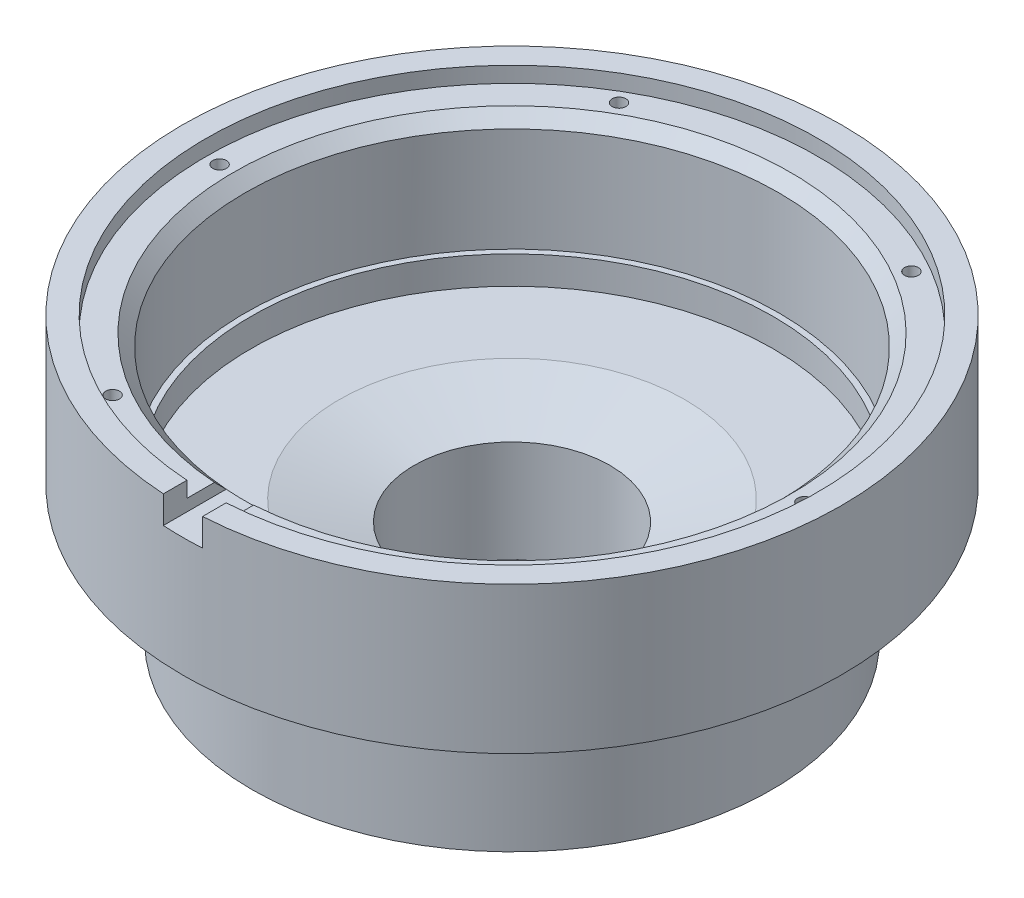
SolidWorks part; units mm, degrees
material "1060 Alloy"
ref_plane "Front Plane" through (0, 0, 0) normal (0, 0, 1) x (1, 0, 0)
ref_plane "Top Plane" through (0, 0, 0) normal (0, 1, 0) x (1, 0, 0)
ref_plane "Right Plane" through (0, 0, 0) normal (1, 0, 0) x (0, 0, -1)
sketch "Sketch7" plane through (0, 0, 0) normal (0, 0, 1) x (1, 0, 0)
  line L0 (0, -30.2319) -> (0, 30.2319) construction
  line L1 (-42.0375, 21.59) -> (-39.0375, 21.59)
  line L2 (-39.0375, 21.59) -> (-39.0375, 19.59)
  line L3 (-39.0375, 19.59) -> (-34.0375, 19.59)
  line L7 (-22.0375, 1.25) -> (-33.2875, 1.25)
  line L8 (-12.5, -1.25) -> (-12.5, -14.25)
  line L9 (-12.5, -14.25) -> (-42.0375, -14.25)
  line L10 (-42.0375, -14.25) -> (-42.0375, 21.59)
  line L11 (-17.2688, 0) -> (0, 0) construction
  line L12 (-22.0375, 1.25) -> (-12.5, -1.25)
  line L13 (-34.0375, 19.59) -> (-34.0375, 4.82)
  line L14 (-34.0375, 4.82) -> (-33.2875, 4.82)
  line L15 (-33.2875, 4.82) -> (-33.2875, 1.25)
  point P4 (0, 0)
  point P19 (-17.2688, 0)
  point P20 (-36.5375, 19.59)
  dimension "D1" = 3
  dimension "D2" = 2
  dimension "D3" = 5
  dimension "D6" = 13
  dimension "D9" = 12.5
  dimension "D5" = 18.34
  dimension "D7" = 2.5
  dimension "D4" = 34.0375
  dimension "D8" = 14.77
  dimension "D10" = 0.75
  dimension "D11" = 12
revolve "Base Motor Housing" add sketch "Sketch7" angle 360 about L0
chamfer "Chamfer1" distance 1.5 angle 45 1 edges at (0, 19.59, -34.0375)
ref_plane "Chamfer plane" through (0, 18.09, 0) normal (0, -1, 0) x (-1, 0, 0)
sketch "Sketch8" plane through (0, 21.59, 0) normal (0, 1, 0) x (1, 0, 0)
  line L0 (0, 0) -> (0, -42.0375) construction
  line L1 (-2.5, -42.0375) -> (2.5, -42.0375)
  line L2 (-2.5, -42.0375) -> (-2.5, -33.9456)
  line L3 (-2.5, -33.9456) -> (2.5, -33.9456)
  line L4 (2.5, -42.0375) -> (2.5, -33.9456)
  circle A0 centre (0, 0) radius 42.0375 construction
  circle A2 centre (0, 0) radius 34.0375 construction
  point P10 (0, -42.0375)
  point P11 (0, 0)
  point P12 (0, 0)
  point P13 (0, 0)
  dimension "D1" = 5
extrude "Wire Hole" cut sketch "Sketch8" against normal up to surface (3.5 mm away) up to plane "Chamfer plane"
sketch "Sketch9" plane through (0, 19.59, 0) normal (0, 1, 0) x (1, 0, 0)
  line L0 (-35.5375, 0) -> (-39.0375, 0) construction
  circle A2 centre (0, 0) radius 37.2875 construction
  circle A3 centre (-37.2875, 0) radius 0.875
  circle A4 centre (-18.6438, 32.2919) radius 0.875
  circle A5 centre (18.6437, 32.2919) radius 0.875
  circle A6 centre (37.2875, 0) radius 0.875
  circle A7 centre (18.6438, -32.2919) radius 0.875
  circle A8 centre (-18.6437, -32.2919) radius 0.875
  arc A9 (2.5, -38.9574) -> (-2.5, -38.9574) centre (0, 0) ccw construction
  arc A10 (2.5, -38.9574) -> (-2.5, -38.9574) centre (0, 0) ccw construction
  arc A11 (2.5, -35.4495) -> (-2.5, -35.4495) centre (0, 0) ccw construction
  arc A14 (2.5, -35.4495) -> (-2.5, -35.4495) centre (0, 0) ccw construction
  point P0 (0, 0)
  point P21 (0, 0)
  point P31 (-37.2875, 0)
  dimension "D2" = 1.75
  dimension "D3" = 6
extrude "Front-Holes" cut sketch "Sketch9" against normal blind 6
sketch "Sketch10" plane through (0, -14.25, 0) normal (0, -1, 0) x (1, 0, 0)
  line L0 (-12.5, 0) -> (-42.0375, 0) construction
  circle A2 centre (0, 0) radius 42.0375 construction
  circle A3 centre (0, 0) radius 42.0375 construction
  circle A4 centre (-27.2687, 0) radius 2.875
  circle A5 centre (-13.6344, 23.6154) radius 2.875
  circle A6 centre (13.6344, 23.6154) radius 2.875
  circle A7 centre (27.2687, 0) radius 2.875
  circle A8 centre (13.6344, -23.6154) radius 2.875
  circle A9 centre (-13.6344, -23.6154) radius 2.875
  circle A10 centre (0, 0) radius 27.2687 construction
  circle A11 centre (0, 0) radius 12.5 construction
  circle A12 centre (0, 0) radius 12.5 construction
  point P22 (0, 0)
  dimension "D1" = 5.75
  dimension "D2" = 6
extrude "Back-Holes" cut sketch "Sketch10" against normal blind 8
sketch "Sketch11" plane through (0, 0, 0) normal (0, 0, 1) x (1, 0, 0)
  line L0 (33.1437, -14.25) -> (33.1437, -2.25)
  line L1 (-42.0375, -14.25) -> (42.0375, -14.25) construction
  line L2 (33.1437, -2.25) -> (42.0375, 2.8848)
  line L3 (42.0375, -14.25) -> (42.0375, 21.59) construction
  line L4 (42.0375, 2.8848) -> (42.0375, -14.25)
  line L5 (42.0375, -14.25) -> (33.1437, -14.25)
  line L6 (12.5, -14.25) -> (30.1437, -14.25) construction
  line L7 (30.1437, -14.25) -> (30.1437, 21.59) construction
  line L8 (39.0375, 21.59) -> (-39.0375, 21.59) construction
  line L9 (33.1437, -2.25) -> (42.0375, -2.25) construction
  line L10 (0, 0) -> (0, -13.4206) construction
  dimension "D1" = 3
  dimension "D2" = 30
  dimension "D3" = 12
revolve "Cut-Revolve1" cut sketch "Sketch11" angle 360 about L10
equation "\"D2@Sketch9\"=\"Back_mount_hole\""
equation "\"Stator_OD\"= 68'No Tolerance given"
equation "\"A\"=18.34 'taken off spec sheet for 06808 (A)"
equation "\"Rotor_ID\"= 34'No Tolerance Given"
equation "\"back_bearing_Thickness\"= 8'randomish, thinnest off mcmaster"
equation "\"D6@Sketch7\"=\"back_bearing_Thickness\"+5"
equation "\"back_bearing_OD\"= 25'currently non-sense"
equation "\"D9@Sketch7\"=\"back_bearing_OD\"*1/2"
equation "\"D5@Sketch7\"=\"A\""
equation "\"Stator_Gap\"= 0.0375'+- 0.0125 (From 1.3.3.1 Kollmorgen manual)"
equation "\"Back_mount_hole\"= 1.75'To be tapped to M2 (USE LOCKTITE)"
equation "\"D1@Back-Holes\" = \"back_bearing_Thickness\""
equation "\"facePlate_Mount_Hole\"= 5.75'To be tapped to M6"
equation "\"D1@Sketch10\"=\"facePlate_Mount_Hole\""
equation "\"final_shaftD\"= 8'NEMA 23 shaft diameter. Should fit with harmonic?"
equation "\"back_bearing_ID\"= 15'Random number"
equation "\"final_shaftL\"= 50'random length. Idk"
equation "\"back_bearing_IDOD\"= 18'Random number, OD of the inner bearing ring"
equation "\"rotor_shaftD\"= \"Rotor_ID\" - (0.0185)*2'+-0.0065 (from manual)"
equation "\"front_bearing_ID\"= 12'random"
equation "\"front_bearing_OD\"= 20'random"
equation "\"front_bearing_IDOD\"= 14'random"
equation "\"front_bearing_Thickness\"= 5'randomish, thinnest off mcmaster"
equation "\"rotor_thickness\"= 2.4'measured off CAD"
equation "\"rotor_height\"= 14.76'+-0.08 taken off spec sheet for 06808 (C)"
equation "\"D4@Sketch7\"=\"Stator_OD\"/2+\"Stator_Gap\""
equation "\"B\"= 8.2'+-0.35 taken off spec sheet for 06808 (C)"
equation "\"D8@Sketch7\"=(\"A\"-\"B\")/2+\"B\"+1.5"
equation "\"D11@Sketch7\"=\"Rotor_ID\"/2-5"
equation "\"D3@Sketch11\"=\"back_bearing_Thickness\"*1.5"
